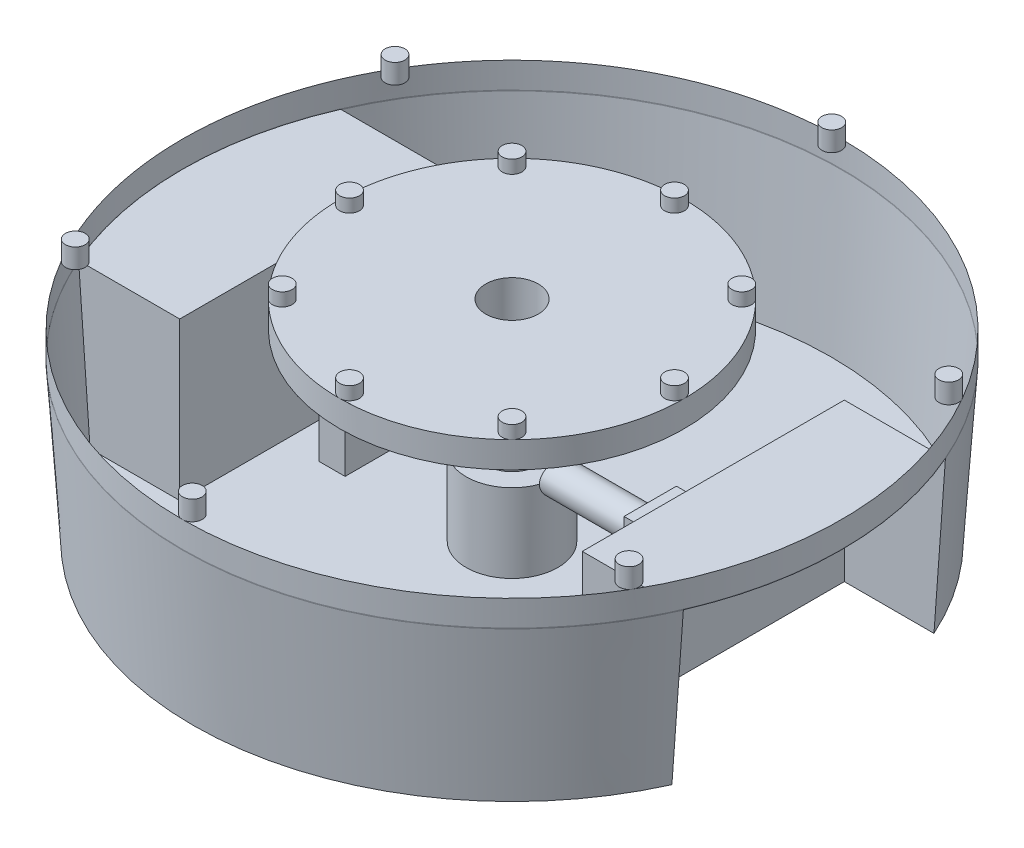
SolidWorks part; units mm, degrees
ref_plane "Front Plane" through (0, 0, 0) normal (0, 0, 1) x (1, 0, 0)
ref_plane "Top Plane" through (0, 0, 0) normal (0, 1, 0) x (1, 0, 0)
ref_plane "Right Plane" through (0, 0, 0) normal (1, 0, 0) x (0, 0, -1)
sketch "Sketch1" plane through (0, 0, 0) normal (0, 1, 0) x (1, 0, 0)
  circle A0 centre (0, 0) radius 41.7512
  point P23 (0, 0)
  dimension "D1" = 83.5025
extrude "Boss-Extrude1" add sketch "Sketch1" along normal blind 6.35
sketch "Sketch2" plane through (0, 6.35, 0) normal (0, 1, 0) x (1, 0, 0)
  line L0 (0, 0) -> (0, 39.37) construction
  circle A1 centre (0, 39.37) radius 2.3813
  circle A2 centre (0, 0) radius 39.37
  circle A3 centre (0, 0) radius 39.37 construction
  circle A4 centre (27.8388, 27.8388) radius 2.3813
  circle A5 centre (39.37, 0) radius 2.3813
  circle A6 centre (27.8388, -27.8388) radius 2.3813
  circle A7 centre (0, -39.37) radius 2.3813
  circle A8 centre (-27.8388, -27.8388) radius 2.3813
  circle A9 centre (-39.37, 0) radius 2.3813
  circle A10 centre (-27.8388, 27.8388) radius 2.3813
  point P21 (0, 0)
  dimension "D1" = 2.3813
  dimension "D2" = 8
extrude "Boss-Extrude2" add sketch "Sketch2" along normal blind 3.175
sketch "Sketch3" plane through (0, 0, 0) normal (0, -1, 0) x (1, 0, 0)
  circle A0 centre (0, 0) radius 79.8512
  dimension "D1" = 159.7025
extrude "Boss-Extrude3" add sketch "Sketch3" along normal blind 6.35
sketch "Sketch4" plane through (0, 0, 0) normal (0, 1, 0) x (1, 0, 0)
  line L0 (0, 0) -> (0, 77.47) construction
  circle A0 centre (0, 77.47) radius 2.3813
  circle A1 centre (67.091, 38.735) radius 2.3813
  circle A2 centre (0, 0) radius 77.47
  circle A3 centre (0, 0) radius 77.47 construction
  circle A4 centre (67.091, -38.735) radius 2.3813
  circle A5 centre (0, -77.47) radius 2.3813
  circle A6 centre (-67.091, -38.735) radius 2.3813
  circle A7 centre (-67.091, 38.735) radius 2.3813
  point P17 (0, 0)
  dimension "D1" = 2.3813
  dimension "D2" = 6
extrude "Boss-Extrude4" add sketch "Sketch4" along normal blind 4.7625
sketch "Sketch5" plane through (0, -6.35, 0) normal (0, -1, 0) x (1, 0, 0)
  circle A2 centre (0, 0) radius 77.3113
  circle A3 centre (0, 0) radius 77.3113
  dimension "D2" = 154.6225
  dimension "D1" = 2.54
extrude "Boss-Extrude5" add sketch "Sketch5" along normal blind 38.1
sketch "Sketch6" plane through (0, 0, 0) normal (1, 0, 0) x (0, 0, -1)
  line L0 (77.3113, -6.35) -> (77.3113, -44.45)
  line L1 (77.3113, -44.45) -> (79.8512, -6.35)
  line L2 (79.8512, -6.35) -> (77.3113, -6.35)
ref_axis "Axis1" through (0, 12.2237, 0) along (0, -1, 0)
revolve "Revolve1" add sketch "Sketch6" angle 360 about axis through (0, 12.2237, 0) along (0, -1, 0)
fillet "Fillet1" radius 2.54 1 edges at (0, -6.35, -79.8512)
sketch "Sketch7" plane through (0, -44.45, 0) normal (0, -1, 0) x (1, 0, 0)
  line L0 (-60.9726, 0) -> (60.9726, 0) construction
  line L1 (48.768, -31.75) -> (48.768, 31.75)
  line L2 (48.768, 31.75) -> (70.4909, 31.75)
  line L3 (48.768, -31.75) -> (70.4909, -31.75)
  line L4 (0, 0) -> (0, 27.0167) construction
  line L5 (-48.768, -31.75) -> (-48.768, 31.75)
  line L6 (-48.768, -31.75) -> (-70.4909, -31.75)
  line L7 (-48.768, 31.75) -> (-70.4909, 31.75)
  line L8 (-70.4909, 31.75) -> (-86.5319, 31.75)
  line L9 (-86.5319, 31.75) -> (-86.5319, -31.75)
  line L10 (-86.5319, -31.75) -> (-70.4909, -31.75)
  line L11 (70.4909, 31.75) -> (86.6858, 31.75)
  line L12 (86.6858, 31.75) -> (86.6858, -31.75)
  line L13 (86.6858, -31.75) -> (70.4909, -31.75)
  circle A0 centre (0, 0) radius 77.3113 construction
  point P5 (0, 0)
  point P9 (48.768, 0)
  dimension "D3" = 21.7229
  dimension "D1" = 63.5
  dimension "D2" = 48.768
extrude "Cut-Extrude1" cut sketch "Sketch7" against normal blind 38.1
sketch "Sketch8" plane through (-48.768, 0, 0) normal (-1, 0, 0) x (0, 0, 1)
  line L0 (0, -6.35) -> (0, -44.45) construction
  line L1 (-31.75, -6.35) -> (31.75, -6.35) construction
  line L2 (-31.75, -44.45) -> (31.75, -44.45) construction
  circle A0 centre (0, -25.4) radius 3.81
  dimension "D1" = 7.62
extrude "Cut-Extrude2" cut sketch "Sketch8" against normal blind 97.536
sketch "Sketch9" plane through (0, 6.35, 0) normal (0, 1, 0) x (1, 0, 0)
  circle A0 centre (0, 0) radius 6.35
  dimension "D1" = 12.7
extrude "Cut-Extrude3" cut sketch "Sketch9" against normal blind 50.8
sketch "Sketch10" plane through (0, -44.45, 0) normal (0, -1, 0) x (1, 0, 0)
  circle A0 centre (0, 0) radius 11.1125
  dimension "D1" = 22.225
extrude "Cut-Extrude4" cut sketch "Sketch10" against normal blind 19.05
sketch "Sketch11" plane through (0, -44.45, 0) normal (0, -1, 0) x (1, 0, 0)
  line L0 (11.1125, 0) -> (48.768, 0) construction
  line L1 (48.768, 31.75) -> (48.768, -31.75) construction
  line L2 (33.793, -6.0421) -> (33.793, 6.6579)
  line L3 (33.793, -6.0421) -> (40.143, -6.0421)
  line L4 (33.793, 6.6579) -> (40.143, 6.6579)
  line L5 (40.143, -6.0421) -> (40.143, 6.6579)
  line L6 (33.793, -6.0421) -> (40.143, 6.6579) construction
  line L7 (33.793, 6.6579) -> (40.143, -6.0421) construction
  line L8 (0, 0) -> (0, 31.9234) construction
  line L9 (-33.793, 6.6579) -> (-40.143, 6.6579)
  line L10 (-40.143, -6.0421) -> (-40.143, 6.6579)
  line L11 (-33.793, -6.0421) -> (-40.143, -6.0421)
  line L12 (-33.793, -6.0421) -> (-33.793, 6.6579)
  circle A0 centre (0, 0) radius 11.1125 construction
  point P7 (36.968, 0.3079)
  dimension "D1" = 6.35
  dimension "D2" = 12.7
extrude "Cut-Extrude5" cut sketch "Sketch11" against normal blind 25.4
sketch "Sketch12" plane through (0, -25.4, 0) normal (0, -1, 0) x (1, 0, 0)
  circle A0 centre (0, 0) radius 11.1125
  circle A1 centre (0, 0) radius 6.35
extrude "Boss-Extrude6" add sketch "Sketch12" against normal blind 6.35
